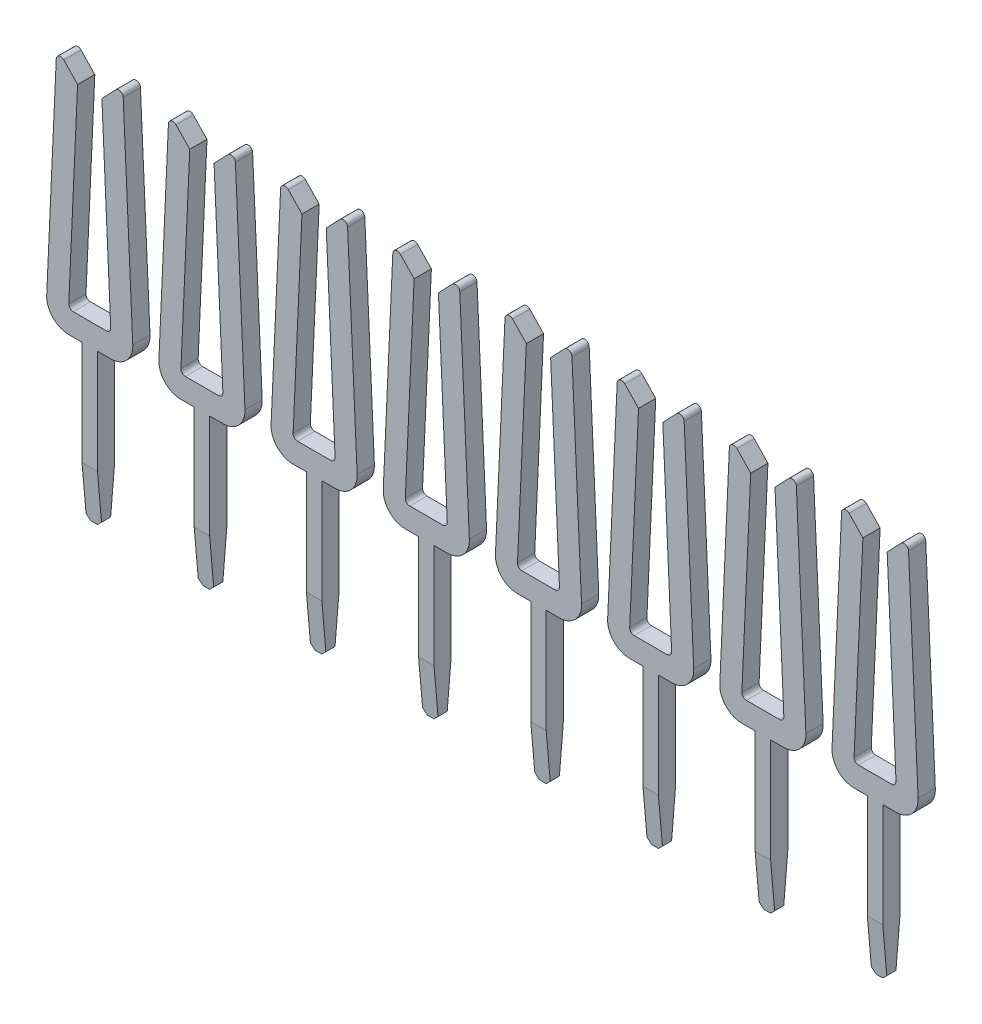
SolidWorks part; units mm, degrees
other "Шпилька"
ref_plane "Front Plane" through (0, 0, 0) normal (0, 0, 1) x (1, 0, 0)
ref_plane "Top Plane" through (0, 0, 0) normal (0, 1, 0) x (1, 0, 0)
ref_plane "Right Plane" through (0, 0, 0) normal (1, 0, 0) x (0, 0, -1)
sketch "Эскиз-Шпилька" plane through (0, 0, 0) normal (0, 0, 1) x (1, 0, 0)
  line L0 (-0.2751, 4.5045) -> (-0.586, 4.8299)
  line L1 (-0.7582, 4.7653) -> (-0.9745, 0.0228)
  line L2 (-0.475, -0.5) -> (-0.175, -0.5)
  line L3 (-0.175, -0.5) -> (-0.175, -3.9)
  line L4 (-0.175, -3.9) -> (-0.075, -4)
  line L5 (0, 4.5045) -> (0, -4) construction
  line L6 (-0.375, 0) -> (0.375, 0)
  line L7 (-0.4749, 0.1045) -> (-0.2751, 4.5045)
  line L8 (0.4749, 0.1045) -> (0.2751, 4.5045)
  line L9 (0.175, -3.9) -> (0.075, -4)
  line L10 (0.175, -0.5) -> (0.175, -3.9)
  line L11 (0.475, -0.5) -> (0.175, -0.5)
  line L12 (0.7582, 4.7653) -> (0.9745, 0.0228)
  line L13 (0.2751, 4.5045) -> (0.586, 4.8299)
  line L14 (-0.075, -4) -> (0.075, -4)
  arc A0 (-0.9745, 0.0228) -> (-0.475, -0.5) centre (-0.475, 0) ccw
  arc A1 (-0.4749, 0.1045) -> (-0.375, 0) centre (-0.375, 0.1) ccw
  arc A2 (-0.586, 4.8299) -> (-0.7582, 4.7653) centre (-0.6583, 4.7608) ccw
  arc A3 (0.586, 4.8299) -> (0.7582, 4.7653) centre (0.6583, 4.7608) cw
  arc A4 (0.4749, 0.1045) -> (0.375, 0) centre (0.375, 0.1) cw
  arc A5 (0.9745, 0.0228) -> (0.475, -0.5) centre (0.475, 0) cw
  point P26 (0, 0)
  point P29 (0, 0)
  point P30 (0, 0)
  point P31 (0, 0)
  point P32 (0, 0)
  point P33 (0, 0)
  point P34 (0, 0)
  point P35 (0, 0)
  point P37 (0, -4)
  dimension "D1" = 2.6
  dimension "D2" = 0.1
  dimension "D6" = 0.1
  dimension "D8" = 0.5
  dimension "D3" = 0.45
  dimension "D4" = 133.7
  dimension "D5" = 4.4
  dimension "D7" = 0.375
  dimension "D9" = 0.3
  dimension "D10" = 3.5
  dimension "D11" = 0.1
  dimension "D12" = 0.1
  dimension "D13" = 0.35
  dimension "D14" = 0.5
extrude "Бобышка-Шпилька" add sketch "Эскиз-Шпилька" along normal blind 0.195 and the other way blind 0.195
chamfer "Фаска1" distance 0.1 angle 85 1 edges at (0, -4, 0.195) first distance on face at (0, -4, 0)
chamfer "Фаска2" distance 0.1 angle 85 1 edges at (0, -4, -0.195) first distance on face at (0, -4, -0.05)
pattern_linear "Линейный массив1" count 8 spacing 2.54 along (-1, 0, 0) of "Бобышка-Шпилька"
